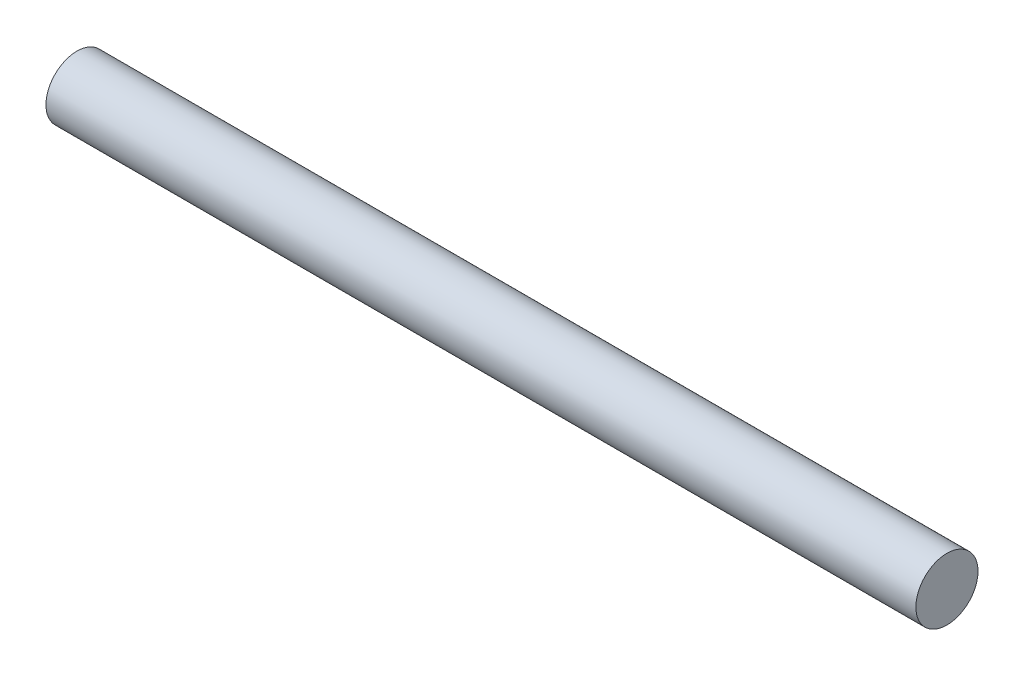
SolidWorks part; units mm, degrees
ref_plane "Front Plane" through (0, 0, 0) normal (0, 0, 1) x (1, 0, 0)
ref_plane "Top Plane" through (0, 0, 0) normal (0, 1, 0) x (1, 0, 0)
ref_plane "Right Plane" through (0, 0, 0) normal (1, 0, 0) x (0, 0, -1)
sketch "Sketch1" plane through (0, 0, 0) normal (1, 0, 0) x (0, 0, -1)
  circle A0 centre (0, 0) radius 5
  dimension "D1" = 10
extrude "Boss-Extrude1" add sketch "Sketch1" along normal blind 140
